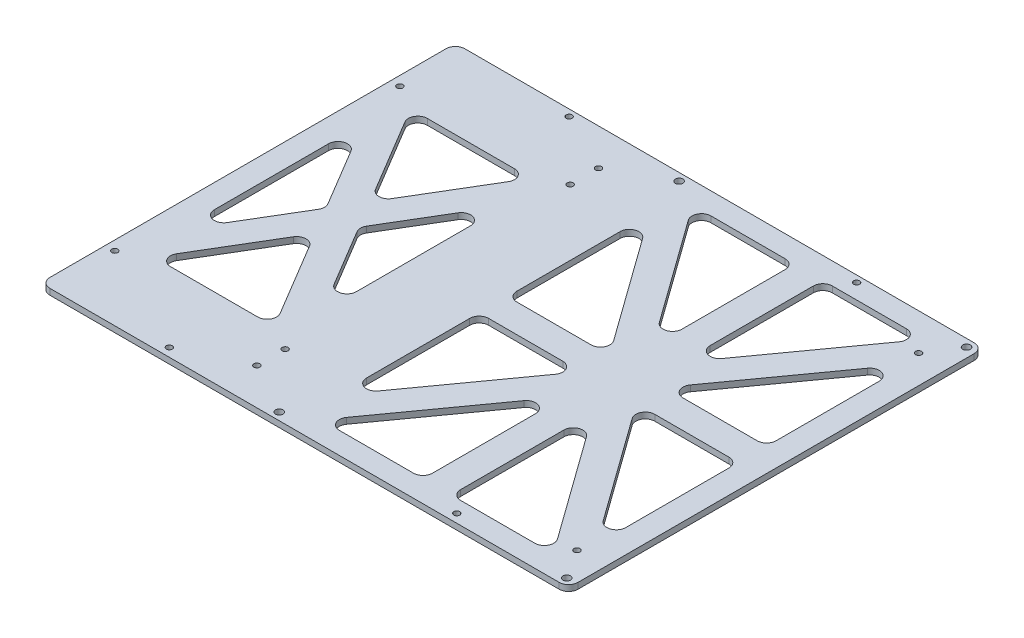
SolidWorks part; units mm, degrees
ref_plane "Front Plane" through (0, 0, 0) normal (0, 0, 1) x (1, 0, 0)
ref_plane "Top Plane" through (0, 0, 0) normal (0, 1, 0) x (1, 0, 0)
ref_plane "Right Plane" through (0, 0, 0) normal (1, 0, 0) x (0, 0, -1)
sketch "Sketch1" plane through (0, 0, 0) normal (0, 1, 0) x (1, 0, 0)
  line L0 (-280, 0) -> (280, 0) construction
  line L1 (-280, -210) -> (-280, 210)
  line L2 (-270, -220) -> (270, -220)
  line L3 (280, -210) -> (280, 210)
  line L4 (-270, 220) -> (270, 220)
  line L5 (0, -220) -> (0, 220) construction
  line L6 (0, -210.96) -> (0, 213) construction
  line L7 (-152.4, -210.96) -> (-152.4, 213) construction
  line L8 (-152.4, -210.96) -> (152.4, -210.96) construction
  line L9 (152.4, -210.96) -> (152.4, 213) construction
  line L10 (-152.4, 213) -> (152.4, 213) construction
  arc A1 (-270, -220) -> (-280, -210) centre (-270, -210) cw
  arc A5 (270, -220) -> (280, -210) centre (270, -210) ccw
  arc A6 (280, 210) -> (270, 220) centre (270, 210) ccw
  arc A7 (-280, 210) -> (-270, 220) centre (-270, 210) cw
  circle A8 centre (-152.4, -210.96) radius 3.175
  circle A9 centre (152.4, -210.96) radius 3.175
  circle A10 centre (152.4, 213) radius 3.175
  circle A11 centre (-152.4, 213) radius 3.175
  point P8 (0, 0)
  dimension "D6" = 10
  dimension "D10" = 304.8
  dimension "D7" = 10
  dimension "D8" = 423.96
  dimension "D9" = 6.35
  dimension "D1" = 560
  dimension "D2" = 440
  dimension "D3" = 152.4
  dimension "D11" = 7
extrude "Body" add sketch "Sketch1" along normal blind 6.35
sketch "Sketch3" plane through (0, 6.35, 0) normal (0, 1, 0) x (1, 0, 0)
  line L0 (117.6, -211.98) -> (117.6, 211.98) construction
  line L1 (-34.8, -211.98) -> (-34.8, 211.98) construction
  line L2 (-34.8, -211.98) -> (270, -211.98) construction
  line L3 (270, -211.98) -> (270, 211.98) construction
  line L4 (-34.8, 211.98) -> (270, 211.98) construction
  line L5 (280, -210) -> (280, 210) construction
  circle A0 centre (-34.8, -211.98) radius 4
  circle A1 centre (270, -211.98) radius 4
  circle A2 centre (270, 211.98) radius 4
  circle A3 centre (-34.8, 211.98) radius 4
  point P10 (117.6, 0)
  dimension "D3" = 8
  dimension "D1" = 423.96
  dimension "D2" = 304.8
  dimension "D4" = 10
sketch "Sketch5" plane through (0, 6.35, 0) normal (0, 1, 0) x (1, 0, 0)
  line L0 (-270, -151.13) -> (-89.43, -151.13) construction
  line L1 (-89.43, -151.13) -> (-89.43, 151.13) construction
  line L2 (-89.43, 151.13) -> (-270, 151.13) construction
  line L3 (-270, 151.13) -> (-270, -151.13) construction
  line L4 (-270, 0) -> (-89.43, 0) construction
  line L6 (-280, 210) -> (-280, -210) construction
  circle A0 centre (-270, -151.13) radius 3.175
  circle A1 centre (-270, 151.13) radius 3.175
  circle A2 centre (-89.43, -151.13) radius 3.175
  circle A3 centre (-89.43, 151.13) radius 3.175
  dimension "D3" = 6.35
  dimension "D1" = 302.26
  dimension "D2" = 180.57
  dimension "D4" = 10
extrude "Electronics Box" cut sketch "Sketch3" against normal up to next
extrude "Battery Charger" cut sketch "Sketch5" against normal up to next
sketch "Sketch6" plane through (0, 6.35, 0) normal (0, 1, 0) x (1, 0, 0)
  line L0 (-255, 60.5351) -> (-255, -60.5351)
  line L1 (-236.4152, -65.6636) -> (-200.2516, -5.1285)
  line L2 (-200.2516, 5.1285) -> (-236.4152, 65.6636)
  line L3 (-179.715, 151.13) -> (-179.715, -151.13) construction
  line L4 (-89.43, 0) -> (-270, 0) construction
  line L5 (-159.1784, 5.1285) -> (-123.0148, 65.6636)
  line L6 (-234.5284, -121.0015) -> (-188.2998, -43.6183)
  line L7 (-171.1302, -43.6183) -> (-124.9016, -121.0015)
  line L8 (-133.4864, -136.13) -> (-225.9436, -136.13)
  line L9 (-270, 151.13) -> (-89.43, 151.13) construction
  line L10 (-89.43, 151.13) -> (-89.43, -151.13) construction
  line L11 (-89.43, -151.13) -> (-270, -151.13) construction
  line L12 (-270, -151.13) -> (-270, 151.13) construction
  line L13 (-89.43, 151.13) -> (-270, -151.13) construction
  line L14 (-89.43, -151.13) -> (-270, 151.13) construction
  line L15 (-123.0148, -65.6636) -> (-159.1784, -5.1285)
  line L16 (-104.43, 60.5351) -> (-104.43, -60.5351)
  line L17 (-171.1302, 43.6183) -> (-124.9016, 121.0015)
  line L18 (-234.5284, 121.0015) -> (-188.2998, 43.6183)
  line L19 (-133.4864, 136.13) -> (-225.9436, 136.13)
  line L20 (-34.8, 211.98) -> (270, 211.98) construction
  line L21 (270, 211.98) -> (270, -211.98) construction
  line L22 (270, -211.98) -> (-34.8, -211.98) construction
  line L23 (-34.8, -211.98) -> (-34.8, 211.98) construction
  line L24 (117.6, 211.98) -> (117.6, -211.98) construction
  line L25 (270, 0) -> (-34.8, 0) construction
  line L26 (-34.8, 211.98) -> (270, -211.98) construction
  line L27 (270, 211.98) -> (-34.8, -211.98) construction
  line L28 (-1.6806, 140.2161) -> (76.9557, 30.8374)
  line L29 (-9.8, 15) -> (68.8363, 15)
  line L30 (-19.8, 25) -> (-19.8, 134.3788)
  line L31 (255, 25) -> (255, 134.3788)
  line L32 (245, 15) -> (166.3637, 15)
  line L33 (236.8806, 140.2161) -> (158.2443, 30.8374)
  line L34 (84.4806, 71.7639) -> (5.8443, 181.1426)
  line L35 (13.9637, 196.98) -> (92.6, 196.98)
  line L36 (221.2363, 196.98) -> (142.6, 196.98)
  line L37 (132.6, 77.6012) -> (132.6, 186.98)
  line L38 (150.7194, 71.7639) -> (229.3557, 181.1426)
  line L39 (102.6, -77.6012) -> (102.6, -186.98)
  line L40 (102.6, 77.6012) -> (102.6, 186.98)
  line L41 (150.7194, -71.7639) -> (229.3557, -181.1426)
  line L42 (132.6, -77.6012) -> (132.6, -186.98)
  line L43 (221.2363, -196.98) -> (142.6, -196.98)
  line L44 (13.9637, -196.98) -> (92.6, -196.98)
  line L45 (84.4806, -71.7639) -> (5.8443, -181.1426)
  line L46 (236.8806, -140.2161) -> (158.2443, -30.8374)
  line L47 (245, -15) -> (166.3637, -15)
  line L48 (255, -25) -> (255, -134.3788)
  line L49 (-19.8, -25) -> (-19.8, -134.3788)
  line L50 (-9.8, -15) -> (68.8363, -15)
  line L51 (-1.6806, -140.2161) -> (76.9557, -30.8374)
  arc A2 (-255, 60.5351) -> (-236.4152, 65.6636) centre (-245, 60.5351) cw
  arc A3 (-236.4152, -65.6636) -> (-255, -60.5351) centre (-245, -60.5351) cw
  arc A4 (-200.2516, 5.1285) -> (-200.2516, -5.1285) centre (-208.8364, 0) cw
  arc A5 (-159.1784, 5.1285) -> (-159.1784, -5.1285) centre (-150.5936, 0) ccw
  arc A6 (-104.43, 60.5351) -> (-123.0148, 65.6636) centre (-114.43, 60.5351) ccw
  arc A7 (-123.0148, -65.6636) -> (-104.43, -60.5351) centre (-114.43, -60.5351) ccw
  arc A8 (-225.9436, -136.13) -> (-234.5284, -121.0015) centre (-225.9436, -126.13) cw
  arc A9 (-124.9016, -121.0015) -> (-133.4864, -136.13) centre (-133.4864, -126.13) cw
  arc A10 (-188.2998, -43.6183) -> (-171.1302, -43.6183) centre (-179.715, -48.7469) cw
  arc A11 (-124.9016, 121.0015) -> (-133.4864, 136.13) centre (-133.4864, 126.13) ccw
  arc A12 (-188.2998, 43.6183) -> (-171.1302, 43.6183) centre (-179.715, 48.7469) ccw
  arc A13 (-225.9436, 136.13) -> (-234.5284, 121.0015) centre (-225.9436, 126.13) ccw
  arc A14 (-1.6806, 140.2161) -> (-19.8, 134.3788) centre (-9.8, 134.3788) ccw
  arc A15 (-9.8, 15) -> (-19.8, 25) centre (-9.8, 25) cw
  arc A16 (68.8363, 15) -> (76.9557, 30.8374) centre (68.8363, 25) ccw
  arc A17 (166.3637, 15) -> (158.2443, 30.8374) centre (166.3637, 25) cw
  arc A18 (245, 15) -> (255, 25) centre (245, 25) ccw
  arc A19 (236.8806, 140.2161) -> (255, 134.3788) centre (245, 134.3788) cw
  arc A20 (13.9637, 196.98) -> (5.8443, 181.1426) centre (13.9637, 186.98) ccw
  arc A21 (102.6, 77.6012) -> (84.4806, 71.7639) centre (92.6, 77.6012) cw
  arc A22 (92.6, 196.98) -> (102.6, 186.98) centre (92.6, 186.98) cw
  arc A23 (221.2363, 196.98) -> (229.3557, 181.1426) centre (221.2363, 186.98) cw
  arc A24 (142.6, 196.98) -> (132.6, 186.98) centre (142.6, 186.98) ccw
  arc A25 (132.6, 77.6012) -> (150.7194, 71.7639) centre (142.6, 77.6012) ccw
  arc A26 (132.6, -77.6012) -> (150.7194, -71.7639) centre (142.6, -77.6012) cw
  arc A27 (142.6, -196.98) -> (132.6, -186.98) centre (142.6, -186.98) cw
  arc A28 (221.2363, -196.98) -> (229.3557, -181.1426) centre (221.2363, -186.98) ccw
  arc A29 (92.6, -196.98) -> (102.6, -186.98) centre (92.6, -186.98) ccw
  arc A30 (102.6, -77.6012) -> (84.4806, -71.7639) centre (92.6, -77.6012) ccw
  arc A31 (13.9637, -196.98) -> (5.8443, -181.1426) centre (13.9637, -186.98) cw
  arc A32 (236.8806, -140.2161) -> (255, -134.3788) centre (245, -134.3788) ccw
  arc A33 (245, -15) -> (255, -25) centre (245, -25) cw
  arc A34 (166.3637, -15) -> (158.2443, -30.8374) centre (166.3637, -25) ccw
  arc A35 (68.8363, -15) -> (76.9557, -30.8374) centre (68.8363, -25) cw
  arc A36 (-9.8, -15) -> (-19.8, -25) centre (-9.8, -25) ccw
  arc A37 (-1.6806, -140.2161) -> (-19.8, -134.3788) centre (-9.8, -134.3788) cw
  dimension "D7" = 10
  dimension "D8" = 10
  dimension "D11" = 10
  dimension "D14" = 10
  dimension "D15" = 10
  dimension "D18" = 10
  dimension "D1" = 15
  dimension "D2" = 15
  dimension "D3" = 15
  dimension "D4" = 15
  dimension "D5" = 15
  dimension "D6" = 15
  dimension "D9" = 15
  dimension "D10" = 15
  dimension "D12" = 15
  dimension "D13" = 15
  dimension "D16" = 15
  dimension "D17" = 15
extrude "Fillets" cut sketch "Sketch6" against normal up to next
sketch "Sketch7" plane through (0, 6.35, 0) normal (0, 1, 0) x (1, 0, 0)
  line L0 (280, -210) -> (280, 210) construction
  line L1 (0, 0) -> (280, 0) construction
  circle A0 centre (250, 181.13) radius 3.175
  circle A1 centre (-89.43, 181.13) radius 3.175
  circle A4 centre (-89.43, -181.13) radius 3.175
  circle A5 centre (250, -181.13) radius 3.175
  point P4 (-89.43, 151.13)
  dimension "D2" = 6.35
  dimension "D1" = 30
  dimension "D3" = 30
extrude "Plant Mounting holes" cut sketch "Sketch7" against normal up to next
